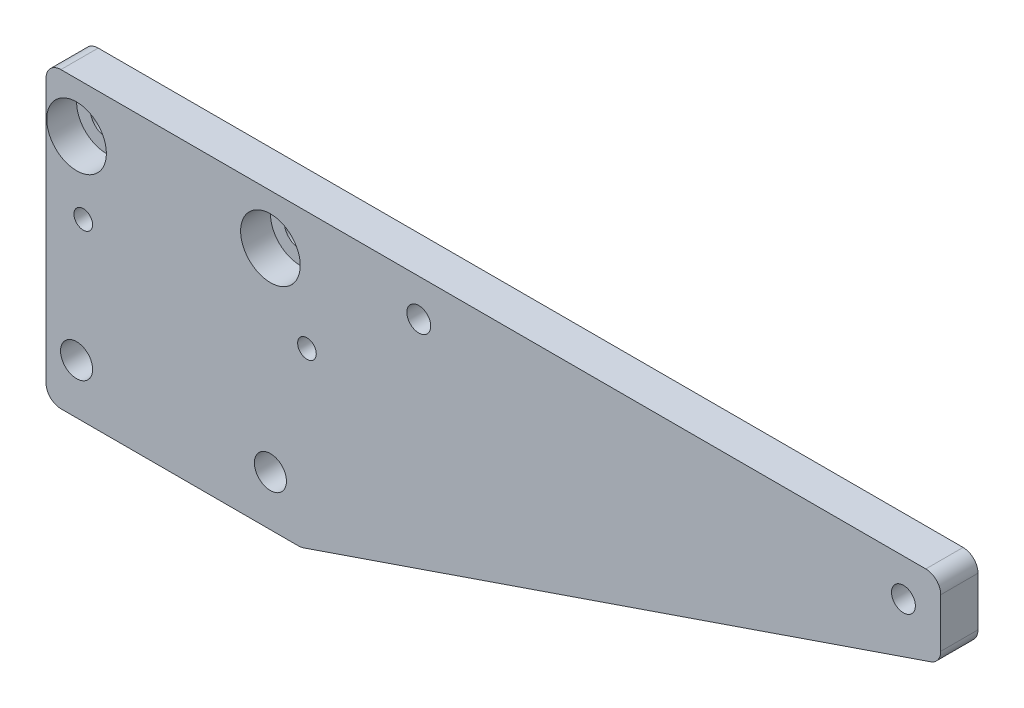
SolidWorks part; units mm, degrees
material "AISI 1045 Steel, cold drawn"
ref_plane "Front Plane" through (0, 0, 0) normal (0, 0, 1) x (1, 0, 0)
ref_plane "Top Plane" through (0, 0, 0) normal (0, 1, 0) x (1, 0, 0)
ref_plane "Right Plane" through (0, 0, 0) normal (1, 0, 0) x (0, 0, -1)
sketch "Sketch1" plane through (0, 0, 0) normal (0, 0, 1) x (1, 0, 0)
  line L0 (17.1, 19.7) -> (102.9, 19.7)
  line L1 (13, -13) -> (-13, -13) construction
  line L2 (13, -13) -> (13, 13) construction
  line L3 (13, 13) -> (-13, 13) construction
  line L4 (-13, -13) -> (-13, 13) construction
  line L5 (13, -13) -> (-13, 13) construction
  line L6 (13, 13) -> (-13, -13) construction
  line L7 (17.1, -19.7) -> (-17.1, -19.7)
  line L8 (17.1, -19.7) -> (17.1, 19.7) construction
  line L9 (17.1, 19.7) -> (-17.1, 19.7)
  line L10 (-17.1, -19.7) -> (-17.1, 19.7)
  line L11 (17.1, -19.7) -> (-17.1, 19.7) construction
  line L12 (17.1, 19.7) -> (-17.1, -19.7) construction
  line L13 (102.9, 19.7) -> (102.9, 9.7)
  line L14 (102.9, 9.7) -> (17.1, -19.7)
  point P0 (0, 0)
  point P6 (0, 0)
  dimension "D1" = 39.4
  dimension "D2" = 120
  dimension "D3" = 34.2
  dimension "D4" = 26
  dimension "D5" = 10
extrude "Boss-Extrude1" add sketch "Sketch1" along normal blind 5
hole_wizard "CBORE for M4 SHCS1" positions "Sketch2" profile "Sketch3" counterbore size "M4" standard "ANSI Metric" end condition through all
sketch "Sketch2" plane through (0, 0, 5) normal (0, 0, 1) x (1, 0, 0)
  point P0 (13, 13)
  point P3 (-13, 13)
sketch "Sketch3" plane through (13, 13, 5) normal (1, 0, 0) x (0, -1, 0)
  line L0 (0, 0) -> (0, 5)
  line L1 (0, 5) -> (2.15, 5)
  line L3 (2.15, 5) -> (2.15, 4)
  line L4 (2.15, 4) -> (4, 4)
  line L5 (4, 4) -> (4, 0)
  line L7 (4, 0) -> (0, 0)
  line L11 (0, -6.35) -> (0, 107.95) construction
  dimension "Thru Hole Dia." = 4.3
  dimension "Thru Hole Depth" = 5
  dimension "C'Bore Dia." = 8
  dimension "C'Bore Depth" = 4
hole_wizard "M4 Clearance Hole1" positions "Sketch10" profile "Sketch11" hole size "M4" standard "ANSI Metric" end condition through all
sketch "Sketch10" plane through (0, 0, 5) normal (0, 0, 1) x (1, 0, 0)
  point P0 (-13, -13)
  point P3 (13, -13)
sketch "Sketch11" plane through (-13, -13, 5) normal (1, 0, 0) x (0, -1, 0)
  line L0 (0, 0) -> (0, 5)
  line L1 (0, 5) -> (2.15, 5)
  line L2 (2.15, 5) -> (2.15, 0)
  line L5 (2.15, 0) -> (0, 0)
  line L11 (0, -6.35) -> (0, 107.95) construction
  dimension "Thru Hole Dia." = 4.3
  dimension "Thru Hole Depth" = 5
hole_wizard "Tap Drill for M3x0.5 Tap1" positions "Sketch4" profile "Sketch5" hole size "M3x0.5" standard "ANSI Metric" end condition through all
sketch "Sketch4" plane through (0, 0, 5) normal (0, 0, 1) x (1, 0, 0)
  line L0 (-12.1, 3.8) -> (17.9, 3.8) construction
  line L2 (102.9, 19.7) -> (-17.1, 19.7) construction
  line L3 (-17.1, 19.7) -> (-17.1, -19.7) construction
  point P0 (-12.1, 3.8)
  point P2 (17.9, 3.8)
  point P17 (2.9, 3.8)
  dimension "D1" = 15.9
  dimension "D2" = 30
  dimension "D3" = 20
sketch "Sketch5" plane through (-12.1, 3.8, 5) normal (1, 0, 0) x (0, -1, 0)
  line L0 (0, 0) -> (0, 5)
  line L1 (0, 5) -> (1.25, 5)
  line L2 (1.25, 5) -> (1.25, 0)
  line L5 (1.25, 0) -> (0, 0)
  line L11 (0, -6.35) -> (0, 107.95) construction
  dimension "Thru Hole Dia." = 2.5
  dimension "Thru Hole Depth" = 5
hole_wizard "M3 Clearance Hole2" positions "Sketch7" profile "Sketch9" hole size "M3" standard "ANSI Metric" end condition through all
sketch "Sketch7" plane through (0, 0, 0) normal (0, 0, -1) x (-1, 0, 0)
  line L1 (-97.9, 14.7) -> (-32.9, 14.7) construction
  line L3 (-102.9, 9.7) -> (-102.9, 19.7) construction
  line L4 (17.1, 19.7) -> (17.1, -19.7) construction
  point P0 (-97.9, 14.7)
  point P2 (-32.9, 14.7)
  point P21 (-102.9, 14.7)
  dimension "D1" = 115
  dimension "D2" = 65
sketch "Sketch9" plane through (97.9, 14.7, 0) normal (1, 0, 0) x (0, 1, 0)
  line L0 (0, 0) -> (0, 5)
  line L1 (0, 5) -> (1.6, 5)
  line L2 (1.6, 5) -> (1.6, 0)
  line L5 (1.6, 0) -> (0, 0)
  line L11 (0, -6.35) -> (0, 107.95) construction
  dimension "Thru Hole Dia." = 3.2
  dimension "Thru Hole Depth" = 5
fillet "Fillet1" radius 2 5 edges at (17.1, -19.7, 2.5) (-17.1, -19.7, 2.5) (102.9, 19.7, 2.5) (-17.1, 19.7, 2.5) (102.9, 9.7, 2.5)
